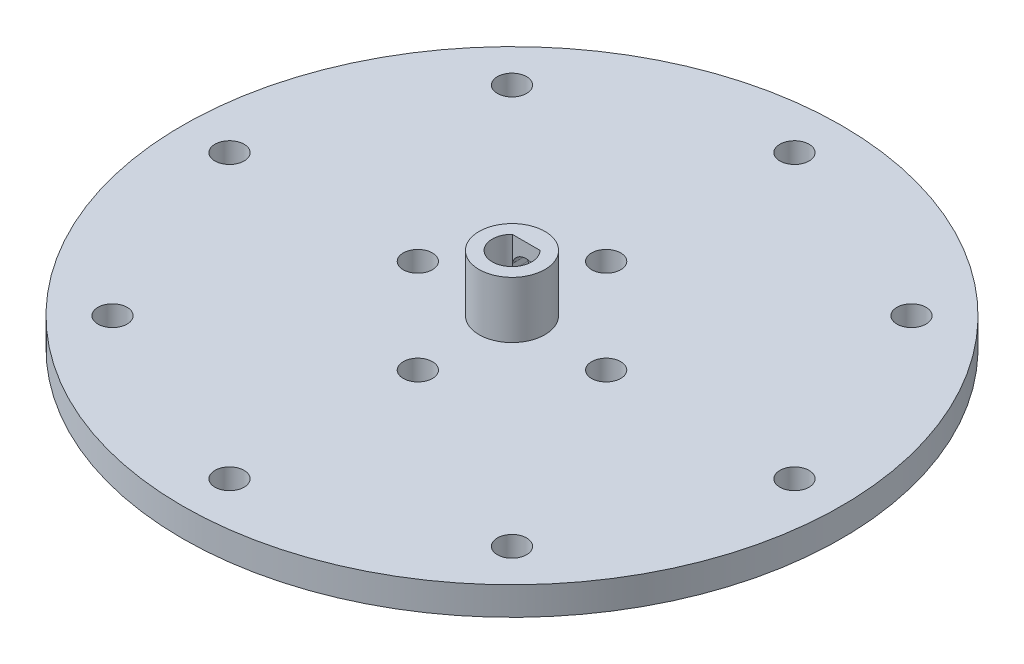
SolidWorks part; units mm, degrees
ref_plane "前视基准面" through (0, 0, 0) normal (0, 0, 1) x (1, 0, 0)
ref_plane "上视基准面" through (0, 0, 0) normal (0, 1, 0) x (1, 0, 0)
ref_plane "右视基准面" through (0, 0, 0) normal (1, 0, 0) x (0, 0, -1)
other "Configuration Table"
sketch "草图1" plane through (0, 0, 0) normal (0, 1, 0) x (1, 0, 0)
  circle A0 centre (0, 0) radius 35
  dimension "D1" = 70
extrude "凸台-拉伸1" add sketch "草图1" along normal blind 3
sketch "草图2" plane through (0, 3, 0) normal (0, 1, 0) x (1, 0, 0)
  line L0 (0, 0) -> (0, 1.5)
  line L1 (-1000, 1.5) -> (49000, 1.5)
  circle A0 centre (0, 0) radius 2.1
  dimension "D1" = 4.2
  dimension "D2" = 1.5
extrude "切除-拉伸1" cut sketch "草图2" against normal blind 3 contours L1 A0 region at (0, 3, 0.1674)
sketch "草图3" plane through (0, 3, 0) normal (0, 1, 0) x (1, 0, 0)
  line L0 (0, 0) -> (0, 1.5)
  line L1 (-1.4697, 1.5) -> (1.4697, 1.5) construction
  line L2 (-1000, 1.5) -> (49000, 1.5)
  circle A0 centre (0, 0) radius 2
  circle A1 centre (0, 0) radius 3.5
  arc M1 (1.4697, 1.5) -> (-1.4697, 1.5) centre (0, 0) cw
  line M2 (-1.4697, 1.5) -> (1.4697, 1.5)
  dimension "D1" = 4
  dimension "D2" = 7
extrude "凸台-拉伸2" add sketch "草图3" along normal blind 6 contours L2 A1 M1 | L2 A1 A0 M2 | A0 L2 M2 region at (0, 3, -2.3925) region at (-2.316, 3, -1.414) region at (0, 3, -1.7023)
sketch "草图4" plane through (0, 0, -1.5) normal (0, 0, 1) x (1, 0, 0)
  line L0 (0, 9) -> (0, 6)
  line L1 (3.5, 9) -> (-3.5, 9) construction
  circle A0 centre (0, 6) radius 1.5
  line M2 (1.4697, 0) -> (1.4697, 9)
  line M4 (-1.4697, 9) -> (-1.4697, 0)
  dimension "D2" = 3
  dimension "D1" = 3
extrude "切除-拉伸2" cut sketch "草图4" against normal blind 6 contours A0 M2 M4 region at (1.4277, 6, -1.5)
sketch "草图5" plane through (0, 3, 0) normal (0, 1, 0) x (1, 0, 0)
  line L0 (-1000, 0) -> (49000, 0)
  line L1 (0, -1000) -> (0, 49000)
  line L2 (0, 0) -> (0, 10)
  line L3 (0, 0) -> (0, 30)
  circle A0 centre (0, 10) radius 1.55
  circle A1 centre (10, 0) radius 1.55
  circle A2 centre (0, -10) radius 1.55
  circle A3 centre (-10, 0) radius 1.55
  circle A4 centre (0, 30) radius 1.55
  circle A5 centre (21.2132, 21.2132) radius 1.55
  circle A6 centre (30, 0) radius 1.55
  circle A7 centre (21.2132, -21.2132) radius 1.55
  circle A8 centre (0, -30) radius 1.55
  circle A9 centre (-21.2132, -21.2132) radius 1.55
  circle A10 centre (-30, 0) radius 1.55
  circle A11 centre (-21.2132, 21.2132) radius 1.55
  point P17 (0, 0)
  point P34 (0, 0)
  dimension "D2" = 3.1
  dimension "D5" = 3.1
  dimension "D1" = 10
  dimension "D4" = 30
  dimension "D3" = 4
  dimension "D6" = 8
extrude "切除-拉伸3" cut sketch "草图5" against normal blind 6 contours L1 A8 | L1 A8 | L1 A2 | L1 A2 | A7 | L0 A6 | L0 A6 | A5 | L1 A4 | L1 A4 | L0 A1 | L0 A1 | L3 A0 L1 | L1 A0 L3 | A9 | A11 | L0 A3 | L0 A3 | L0 A10 | L0 A10 region at (-0.6578, 3, -30) region at (0.6578, 3, -30) region at (-0.6578, 3, -10) region at (0.6578, 3, -10) region at (30, 3, -0.6578) region at (30, 3, 0.6578) region at (10, 3, -0.6578) region at (10, 3, 0.6578) region at (0.6578, 3, 30) region at (-0.6578, 3, 30) region at (0.6578, 3, 10) region at (-0.6578, 3, 10) region at (-10, 3, 0.6578) region at (-10, 3, -0.6578) region at (-30, 3, 0.6578) region at (-30, 3, -0.6578) region at (21.2132, 3, -21.2132) region at (21.2132, 3, 21.2132) region at (-21.2132, 3, 21.2132) region at (-21.2132, 3, -21.2132)
